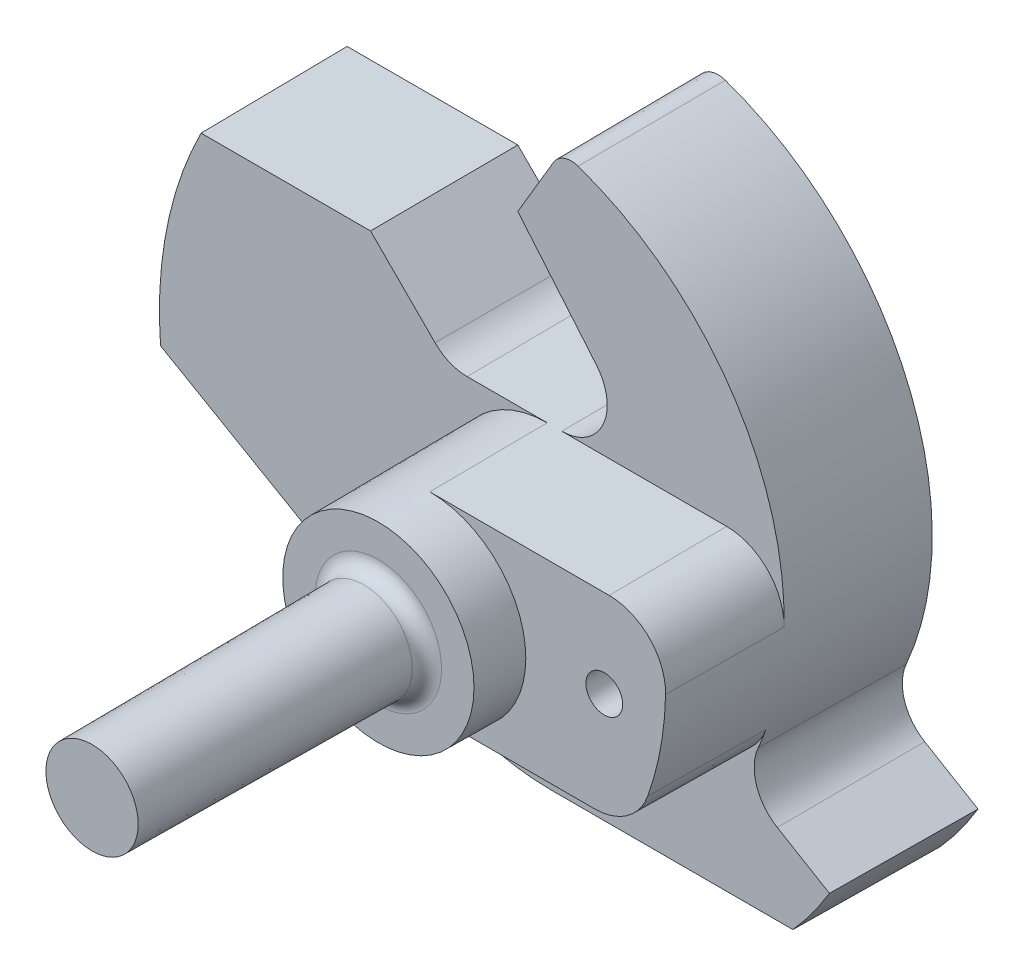
SolidWorks part; units mm, degrees
material "Zamak3"
ref_plane "Front Plane" through (0, 0, 0) normal (0, 0, 1) x (1, 0, 0)
ref_plane "Top Plane" through (0, 0, 0) normal (0, 1, 0) x (1, 0, 0)
ref_plane "Right Plane" through (0, 0, 0) normal (1, 0, 0) x (0, 0, -1)
sketch "Sketch1" plane through (0, 0, 0) normal (0, 0, 1) x (1, 0, 0)
  line L0 (-1.925, 1.925) -> (-3.048, 3.048)
  line L1 (0.2536, 1.7018) -> (-1.3862, 1.7018)
  line L2 (-0.5353, 4.5895) -> (0.8374, 2.9536)
  line L3 (0.088, 5.6456) -> (-0.5353, 4.5895)
  line L4 (4.9121, -2.921) -> (3.9907, -2.3731)
  line L5 (0.0681, -3.81) -> (4.2597, -3.81)
  line L6 (-6.7105, -0.5251) -> (-1.9639, -3.2655)
  line L7 (-3.048, 3.048) -> (-6.0013, 3.048)
  line L8 (0, 0) -> (0, 1.3303) construction
  line L9 (0, 0) -> (2.2266, 0) construction
  arc A0 (-1.925, 1.925) -> (-1.3862, 1.7018) centre (-1.3862, 2.4638) ccw
  arc A1 (0.2536, 1.7018) -> (0.8374, 2.9536) centre (0.2536, 2.4638) ccw
  arc A2 (0.5415, 5.8118) -> (0.088, 5.6456) centre (0.4161, 5.452) ccw
  arc A3 (3.6697, -1.3715) -> (0.5415, 5.8118) centre (-1.2134, 0.7747) ccw
  arc A4 (3.6697, -1.3715) -> (3.9907, -2.3731) centre (4.3964, -1.6908) ccw
  arc A5 (4.2597, -3.81) -> (4.9121, -2.921) centre (0, 0) ccw
  arc A6 (-1.9639, -3.2655) -> (0.0681, -3.81) centre (0.0681, 0.254) ccw
  arc A7 (-6.0013, 3.048) -> (-6.7105, -0.5251) centre (0, 0) ccw
  circle A8 centre (0, 0) radius 1.7018 construction
  dimension "D1" = 6.731
  dimension "D2" = 5.715
  dimension "D3" = 5.334
  dimension "D14" = 0.7938
  dimension "D15" = 4.064
  dimension "D16" = 0.762
  dimension "D17" = 0.381
  dimension "D4" = 1.2134
  dimension "D5" = 0.7747
  dimension "D6" = 30.552
  dimension "D7" = 2.794
  dimension "D8" = 40
  dimension "D9" = 2.54
  dimension "D10" = 1.7018
  dimension "D11" = 45
  dimension "D12" = 3.048
  dimension "D13" = 30.738
  dimension "D18" = 30
  dimension "D19" = 3.81
  dimension "D20" = 3.81
extrude "Extrude1" add sketch "Sketch1" along normal blind 2.54
sketch "Sketch2" plane through (0, 0, 2.54) normal (0, 0, 1) x (1, 0, 0)
  circle A0 centre (0, 0) radius 1.7018
  circle A1 centre (0, 0) radius 1.7018 construction
extrude "Extrude2" add sketch "Sketch2" along normal blind 2.921
sketch "Sketch6" plane through (0, 0, 2.54) normal (0, 0, 1) x (1, 0, 0)
  line L0 (0.0681, -3.81) -> (4.2597, -3.81) construction
  line L1 (0, 1.7018) -> (3.1036, 1.7018)
  line L2 (0, 0) -> (3.0958, 0) construction
  line L3 (0, -1.7018) -> (2.8501, -1.7018)
  circle A0 centre (0, 0) radius 1.7018 construction
  arc A1 (0, -1.7018) -> (0, 1.7018) centre (0, 0) ccw
  arc A2 (3.6697, -1.3715) -> (0.5415, 5.8118) centre (-1.2134, 0.7747) ccw construction
  arc A4 (3.8062, -1.0295) -> (4.1194, 0.6649) centre (-1.2134, 0.7747) ccw
  arc A7 (3.1036, 1.7018) -> (4.1194, 0.6649) centre (3.1036, 0.6858) cw
  arc A8 (2.8501, -1.7018) -> (3.8062, -1.0295) centre (2.8501, -0.6858) ccw
  dimension "D1" = 1.016
  dimension "D3" = 0
extrude "Extrude5" add sketch "Sketch6" along normal blind 2.032
sketch "Sketch3" plane through (0, 0, 5.461) normal (0, 0, 1) x (1, 0, 0)
  circle A0 centre (0, 0) radius 0.889
  dimension "D1" = 1.778
extrude "Extrude3" add sketch "Sketch3" along normal blind 4.953
sketch "Sketch4" plane through (0, 0, 0) normal (0, 0, -1) x (-1, 0, 0)
  line L0 (0, 0) -> (0, 0.7366) construction
  line L1 (0, 0) -> (-0.311, 0.7509)
  line L3 (0, 0) -> (0.311, 0.7509)
  circle A0 centre (0, 0) radius 0.7366 construction
  circle A1 centre (0, 0) radius 1.27 construction
  arc A2 (0.311, 0.7509) -> (0.1635, 0.7962) centre (0, 0) ccw
  arc A3 (-0.1635, 0.7962) -> (0.1635, 0.7962) centre (0, 0.9906) ccw
  arc A4 (-0.1635, 0.7962) -> (-0.311, 0.7509) centre (0, 0) ccw
  dimension "D1" = 1.4732
  dimension "D2" = 2.54
  dimension "D5" = 0.8128
  dimension "D6" = 0.254
  dimension "D3" = 45
  dimension "D4" = 22.5
  dimension "D7" = 0.9906
extrude "Extrude4" cut sketch "Sketch4" against normal blind 4.8199
pattern_circular "CirPattern1" count 8 over 360 about axis through (0, 0, 0) along (0, 0, 1) of "Extrude4"
sketch "Sketch14" plane through (0, 0, 0) normal (0, 0, -1) x (-1, 0, 0)
  line L0 (-0.7309, 0.3556) -> (0.7309, 0.3556)
  circle A0 centre (0, 0) radius 0.7366 construction
  arc A1 (-0.1635, 0.7962) -> (0.1635, 0.7962) centre (0, 0.9906) ccw construction
  arc A2 (-0.6786, 0.4474) -> (-0.7962, 0.1635) centre (0, 0) ccw construction
  arc A3 (0.7962, 0.1635) -> (0.6786, 0.4474) centre (0, 0) ccw construction
  arc A4 (0.7309, 0.3556) -> (-0.7309, 0.3556) centre (0, 0) ccw
  dimension "D1" = 1.4732
  dimension "D2" = 0.381
extrude "Extrude13" add sketch "Sketch14" against normal up to surface (4.8199 mm away) up to face at (0, 0, 4.8199)
draft "Draft8" [suppressed] type of draft neutral plane draft angle 0.25 faces to draft 11 parameters "D1"=0.25
sketch "Sketch7" plane through (0, 0, 4.572) normal (0, 0, 1) x (1, 0, 0)
  line L0 (0, 0) -> (3.0191, 0.1445) construction
  line L1 (0, 0) -> (2.8865, -0.8968) construction
  line L2 (0, 0) -> (2.7876, 1.1684) construction
  circle A0 centre (2.7876, 1.1684) radius 0.3175 construction
  circle A1 centre (3.0191, 0.1445) radius 0.3175
  circle A2 centre (2.8865, -0.8968) radius 0.3175 construction
  circle A3 centre (0, 0) radius 3.0226 construction
  dimension "D1" = 0.635
  dimension "D2" = 6.0452
  dimension "D3" = 1.1684
  dimension "D4" = 20
  dimension "D5" = 40
extrude "Extrude6" cut sketch "Sketch7" against normal through all
sketch "Sketch11" plane through (0, 0, 0) normal (0, 0, -1) x (-1, 0, 0)
  arc A0 (-2.9836, -0.6484) -> (-3.2162, 0.9134) centre (-3.0191, 0.1445) ccw
  arc A2 (-3.5964, 0.3797) -> (-3.2162, 0.9134) centre (-3.0901, 0.4213) cw
  arc A3 (-0.3744, 5.332) -> (-3.2047, -1.1671) centre (1.2134, 0.7747) ccw
  arc A4 (-3.5964, 0.3797) -> (-3.5028, -0.2487) centre (1.2134, 0.7747) ccw
  arc A5 (-3.5028, -0.2487) -> (-2.9836, -0.6484) centre (-3.0064, -0.141) ccw
  dimension "D1" = 1.5875
  dimension "D3" = 0.508
  dimension "D2" = 0.508
extrude "Extrude10" cut sketch "Sketch11" against normal blind 2.54
sketch "Sketch13" plane through (0, 0, 0) normal (0, 0, -1) x (-1, 0, 0)
  line L0 (6.7105, -0.5251) -> (1.9639, -3.2655) construction
  line L1 (2.9307, -1.2409) -> (5.1818, 0.0588)
  line L17 (5.1635, 1.778) -> (3.5741, 1.778)
  line L18 (3.5741, 1.778) -> (2.823, 1.027)
  line L19 (1.3862, 0.4318) -> (-0.2536, 0.4318)
  line L21 (-2.5154, -2.54) -> (-0.0681, -2.54)
  line L22 (1.3289, -2.1657) -> (5.4567, 0.2175)
  line L23 (4.7874, 1.778) -> (3.7845, 1.778)
  line L24 (3.4253, 1.6292) -> (2.823, 1.027)
  arc A0 (2.1901, -0.6553) -> (2.9307, -1.2409) centre (2.6767, -0.8009) ccw
  arc A9 (2.1901, -0.6553) -> (2.2694, 0.2751) centre (0, 0) ccw
  arc A10 (2.4962, 0.7618) -> (2.2694, 0.2751) centre (2.7737, 0.3363) ccw
  arc A11 (3.7845, 1.778) -> (3.4253, 1.6292) centre (3.7845, 1.27) ccw
  arc A12 (4.7874, 1.778) -> (5.2784, 1.4003) centre (4.7874, 1.27) cw
  arc A13 (5.1818, 0.0588) -> (5.4332, 0.5499) centre (4.9278, 0.4987) ccw
  arc A16 (1.3862, 0.4318) -> (2.823, 1.027) centre (1.3862, 2.4638) ccw
  arc A17 (-2.2311, 2.9314) -> (-0.2536, 0.4318) centre (-0.2536, 2.4638) ccw
  arc A18 (-2.2311, 2.9314) -> (-2.5071, -0.8605) centre (1.2134, 0.7747) ccw
  arc A19 (-2.5154, -2.54) -> (-2.5071, -0.8605) centre (-4.3964, -1.6908) ccw
  arc A20 (-0.0681, -2.54) -> (1.3289, -2.1657) centre (-0.0681, 0.254) ccw
  arc A21 (5.4567, 0.2175) -> (5.1635, 1.778) centre (0, 0) ccw
  arc A22 (2.4962, 0.7618) -> (2.823, 1.027) centre (1.3862, 2.4638) ccw
  arc A27 (5.4332, 0.5499) -> (5.2784, 1.4003) centre (0, 0) ccw
  dimension "D2" = 2.286
  dimension "D3" = 0.508
  dimension "D5" = 0.508
  dimension "D4" = 1.27
  dimension "D1" = 1.27
extrude "Extrude12" cut sketch "Sketch13" against normal blind 1.27
draft "Draft5" type of draft neutral plane draft angle 1 faces to draft 4 face at (3.2797, -0.496, 1.27) face at (3.5548, 0.0648, 1.27) face at (3.455, 0.6813, 1.27) face at (2.667, 0.1969, 1.27) neutral plane through (0.8965, 0.3169, 2.54) neutral plane normal (0, 0, -1) parameters "D1"=1
draft "Draft6" type of draft neutral plane draft angle 1 faces to draft 11 face at (-2.663, 0.8901, 0.635) face at (-2.348, 0.5347, 0.635) face at (-2.2537, -0.1921, 0.635) face at (-2.461, -1.0738, 0.635) face at (-4.0563, -0.591, 0.635) face at (-5.3438, 0.2858, 0.635) face at (-5.3643, 0.9766, 0.635) face at (-5.065, 1.6309, 0.635) face at (-4.2859, 1.778, 0.635) face at (-3.5975, 1.7215, 0.635) face at (-3.1241, 1.3281, 0.635) neutral plane through (0, 0, 1.27) neutral plane normal (0, 0, -1) parameters "D1"=1
draft "Draft7" type of draft neutral plane draft angle 0.5 faces to draft 21 face at (0.889, 0, 10.414) face at (1.7018, 0, 5.461) face at (1.425, -1.7018, 3.556) face at (4.5967, -3.3734, 1.27) face at (2.1639, -3.81, 1.27) face at (-0.9659, -3.6046, 1.27) face at (-4.3372, -1.8953, 1.27) face at (-6.4791, 1.2859, 1.27) face at (-4.5247, 3.048, 1.27) face at (-2.4865, 2.4865, 1.27) face at (-1.6667, 1.7866, 1.27) face at (0.2999, 5.7692, 1.27) face at (-0.2237, 5.1176, 1.27) face at (0.151, 3.7716, 1.27) face at (0.7449, 2.2347, 1.27) face at (0.4928, 1.7018, 2.413) face at (3.7205, 1.2901, 3.556) face at (3.3813, -1.4413, 3.556) face at (4.4514, -2.647, 1.27) face at (3.7354, -1.9027, 1.27) face at (3.3441, 1.1754, 2.413) neutral plane through (0, 0, 0) neutral plane normal (0, 0, -1) reverse direction yes parameters "D1"=0.5
fillet "Fillet1" radius 0.254 1 edges at (0.8413, 0, 5.461)
chamfer "Chamfer1" distance 0.381 angle 60 1 edges at (0, 0.3556, 0)
sketch "Sketch16" plane through (0, 0, 0) normal (0, 0, -1) x (-1, 0, 0)
  line L0 (0.7309, 0.3556) -> (-0.7309, 0.3556) construction
  line L1 (0.7309, 0.3556) -> (-0.7309, 0.3556)
  arc A0 (-0.7309, 0.3556) -> (0.7309, 0.3556) centre (0, 0) ccw
extrude "Extrude14" cut sketch "Sketch16" against normal blind 0.6604
sketch "Sketch17" plane through (0, 0, 0.6604) normal (0, 0, -1) x (-1, 0, 0)
  line L0 (0.7309, 0.3556) -> (-0.7309, 0.3556) construction
  line L1 (0.7309, 0.3556) -> (0.6451, 0.3556)
  line L2 (-0.6451, 0.3556) -> (-0.7309, 0.3556)
  arc A0 (-0.3436, 0.7366) -> (0.3436, 0.7366) centre (0, 0) ccw construction
  arc A1 (-0.7309, 0.3556) -> (0.7309, 0.3556) centre (0, 0) ccw
  arc A2 (-0.6451, 0.3556) -> (0.6451, 0.3556) centre (0, 0) ccw
  dimension "D1" = 0.7366
extrude "Boss-Extrude1" add sketch "Sketch17" against normal up to surface (4.1595 mm away) up to face at (0, -0.252, 4.8199)
sketch "Sketch18" plane through (0, 0, 0) normal (0, 0, -1) x (-1, 0, 0)
  line L0 (0.7309, 0.3556) -> (-0.7309, 0.3556) construction
  line L1 (0.7309, 0.3556) -> (-0.7309, 0.3556)
  arc A0 (-0.3436, 0.7366) -> (0.3436, 0.7366) centre (0, 0) ccw construction
  arc A1 (-0.7309, 0.3556) -> (0.7309, 0.3556) centre (0, 0) ccw
extrude "Cut-Extrude1" cut sketch "Sketch18" against normal blind 1.5
chamfer "Chamfer3" distance 0.1016 angle 45 1 edges at (0, -0.7366, 1.5)
chamfer "Chamfer4" distance 0.3048 angle 45 1 edges at (0, -0.8128, 0)
